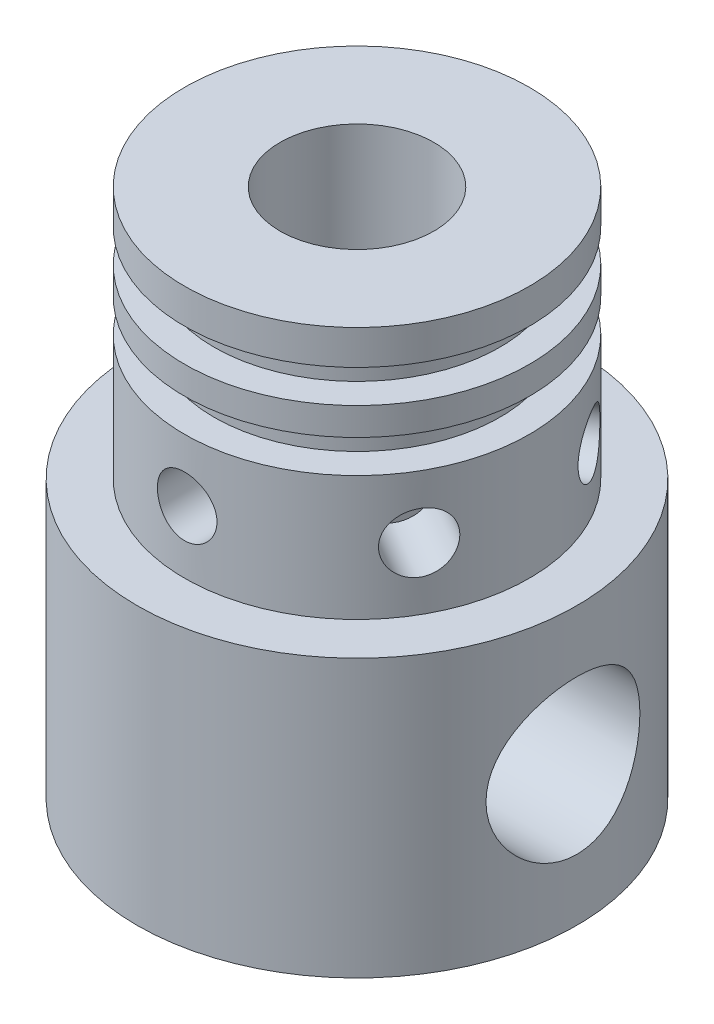
SolidWorks part; units mm, degrees
ref_plane "Front Plane" through (0, 0, 0) normal (0, 0, 1) x (1, 0, 0)
ref_plane "Top Plane" through (0, 0, 0) normal (0, 1, 0) x (1, 0, 0)
ref_plane "Right Plane" through (0, 0, 0) normal (1, 0, 0) x (0, 0, -1)
sketch "Sketch1" plane through (0, 0, 0) normal (0, 0, 1) x (1, 0, 0)
  line L0 (0, -19.1312) -> (15.875, -19.1312)
  line L1 (15.875, -19.1312) -> (15.875, 0.8688)
  line L2 (15.875, 0.8688) -> (12.45, 0.8688)
  line L3 (12.45, 0.8688) -> (12.45, 9.8688)
  line L4 (12.45, 9.8688) -> (10.3187, 9.8688)
  line L5 (10.3187, 9.8688) -> (10.3187, 12.25)
  line L6 (10.3187, 12.25) -> (12.45, 12.25)
  line L7 (12.45, 12.25) -> (12.45, 14.25)
  line L8 (12.45, 14.25) -> (10.3188, 14.25)
  line L9 (10.3188, 14.25) -> (10.3188, 16.6313)
  line L10 (10.3188, 16.6313) -> (12.45, 16.6313)
  line L11 (12.45, 16.6313) -> (12.45, 19.1313)
  line L12 (12.45, 19.1313) -> (0, 19.1312)
  line L13 (0, 19.1312) -> (0, -19.1312)
  line L14 (0, -8.095) -> (0, 15.2312) construction
  line L15 (12.7, 19.4771) -> (12.7, -5.4015) construction
  line L16 (10.3187, 11.0594) -> (12.7, 11.0594) construction
  point P18 (0, 0)
  dimension "D1" = 12.7
  dimension "D2" = 0.5
  dimension "D3" = 31.75
  dimension "D4" = 20
  dimension "D5" = 20.6375
  dimension "D6" = 2
  dimension "D7" = 2.5
  dimension "D8" = 9
revolve "Revolve1" add sketch "Sketch1" angle 360 about L14
sketch "Sketch2" plane through (0, 0, 0) normal (1, 0, 0) x (0, 0, -1)
  line L0 (0, 0.8688) -> (0, -19.1312) construction
  line L1 (15.875, 0.8688) -> (-15.875, 0.8688) construction
  line L2 (-15.875, -19.1312) -> (15.875, -19.1312) construction
  circle A0 centre (0, -9.1312) radius 5.5562
  dimension "D1" = 11.1125
extrude "Cut-Extrude1" cut sketch "Sketch2" against normal through all both and the other way through all
sketch "Sketch3" plane through (0, 19.1313, 0) normal (0, 1, 0) x (1, 0, 0)
  line L0 (-14.8709, 5.5563) -> (14.8709, 5.5563) construction
  circle A0 centre (0, 0) radius 5.5563
  arc A1 (14.8709, -5.5562) -> (14.8709, 5.5563) centre (0, 0) ccw construction
  arc A2 (14.8709, -5.5562) -> (14.8709, 5.5563) centre (0, 0) ccw construction
  arc A3 (-14.8709, 5.5563) -> (-14.8709, -5.5562) centre (0, 0) ccw construction
  arc A4 (-14.8709, 5.5563) -> (-14.8709, -5.5562) centre (0, 0) ccw construction
extrude "Cut-Extrude2" cut sketch "Sketch3" against normal up to next
ref_plane "Plane1" through (0, 0, 12.45) normal (0, 0, 1) x (1, 0, 0)
sketch "Sketch4" plane through (0, 0, 12.45) normal (0, 0, 1) x (1, 0, 0)
  line L0 (0, 0.8688) -> (0, 9.8688) construction
  line L1 (15.875, 0.8688) -> (-15.875, 0.8688) construction
  line L2 (12.45, 9.8688) -> (-12.45, 9.8688) construction
  circle A0 centre (0, 5.3688) radius 2.15
  dimension "D1" = 4.3
extrude "Cut-Extrude3" cut sketch "Sketch4" against normal blind 5
pattern_circular "CirPattern1" count 6 over 360 about axis through (0, -8.095, 0) along (0, -1, 0) of "Cut-Extrude3"
